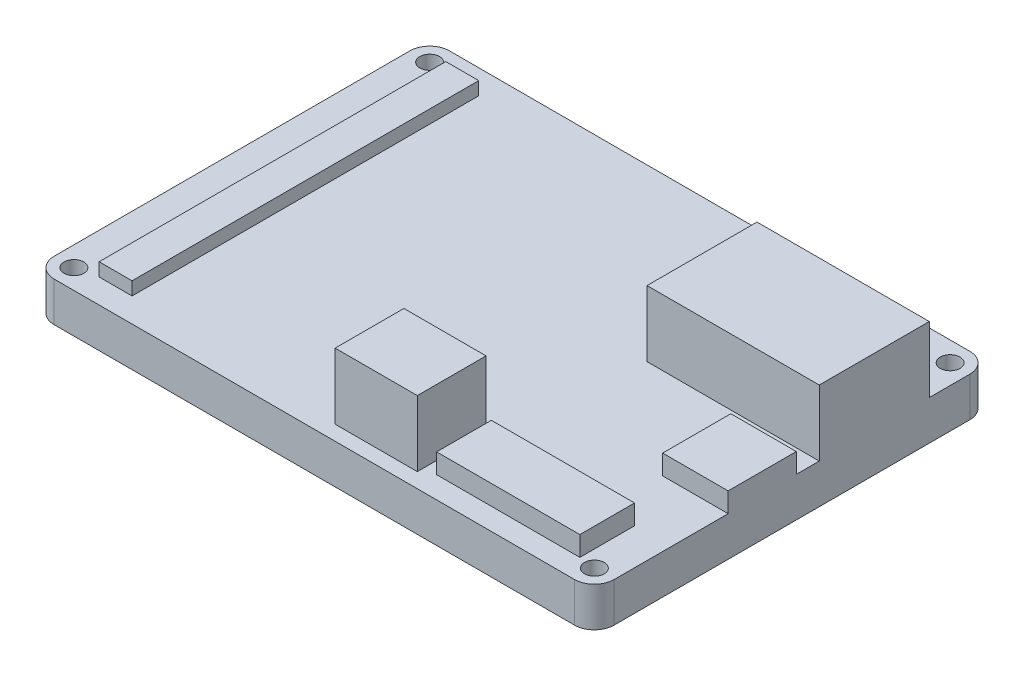
SolidWorks part; units mm, degrees
ref_plane "Front Plane" through (0, 0, 0) normal (0, 0, 1) x (1, 0, 0)
ref_plane "Top Plane" through (0, 0, 0) normal (0, 1, 0) x (1, 0, 0)
ref_plane "Right Plane" through (0, 0, 0) normal (1, 0, 0) x (0, 0, -1)
sketch "Sketch1" plane through (0, 0, 0) normal (0, 1, 0) x (1, 0, 0)
  line L1 (-39.5, -30) -> (39.5, -30)
  line L2 (-42.5, -27) -> (-42.5, 27)
  line L3 (-39.5, 30) -> (39.5, 30)
  line L4 (42.5, -27) -> (42.5, 27)
  line L5 (-42.5, -30) -> (42.5, 30) construction
  line L6 (-42.5, 30) -> (42.5, -30) construction
  line L7 (39.5, -27) -> (-39.5, -27) construction
  line L8 (39.5, -27) -> (39.5, 27) construction
  line L9 (39.5, 27) -> (-39.5, 27) construction
  line L10 (-39.5, -27) -> (-39.5, 27) construction
  line L11 (39.5, -27) -> (-39.5, 27) construction
  line L12 (39.5, 27) -> (-39.5, -27) construction
  arc A0 (-42.5, -27) -> (-39.5, -30) centre (-39.5, -27) ccw
  arc A1 (42.5, -27) -> (39.5, -30) centre (39.5, -27) cw
  arc A2 (42.5, 27) -> (39.5, 30) centre (39.5, 27) ccw
  arc A3 (-39.5, 30) -> (-42.5, 27) centre (-39.5, 27) ccw
  circle A4 centre (-39.5, 27) radius 1.5
  circle A5 centre (39.5, 27) radius 1.5
  circle A6 centre (39.5, -27) radius 1.5
  circle A7 centre (-39.5, -27) radius 1.5
  point P0 (0, 0)
  point P18 (0, 0)
  dimension "D3" = 3
  dimension "D4" = 3
  dimension "D1" = 85
  dimension "D2" = 60
extrude "Boss-Extrude1" add sketch "Sketch1" along normal blind 3 and the other way blind 3
sketch "Sketch2" plane through (0, 0, 0) normal (0, 1, 0) x (1, 0, 0)
  line L1 (-31.3605, -26.3126) -> (-36.3605, -26.3126)
  line L2 (-31.3605, -26.3126) -> (-31.3605, 26.3126)
  line L3 (-31.3605, 26.3126) -> (-36.3605, 26.3126)
  line L4 (-36.3605, -26.3126) -> (-36.3605, 26.3126)
  line L5 (-31.3605, -26.3126) -> (-36.3605, 26.3126) construction
  line L6 (-31.3605, 26.3126) -> (-36.3605, -26.3126) construction
  point P0 (-33.8605, 0)
  dimension "D1" = 5
extrude "Boss-Extrude2" add sketch "Sketch2" along normal blind 5
sketch "Sketch3" plane through (0, 0, 0) normal (0, 1, 0) x (1, 0, 0)
  line L0 (42.5, -27) -> (42.5, 27) construction
  line L1 (16.3563, 4.1414) -> (42.5, 4.1414)
  line L2 (16.3563, 4.1414) -> (16.3563, 20.8379)
  line L3 (16.3563, 20.8379) -> (42.5, 20.8379)
  line L4 (42.5, 4.1414) -> (42.5, 20.8379)
  line L5 (16.3563, 4.1414) -> (42.5, 20.8379) construction
  line L6 (16.3563, 20.8379) -> (42.5, 4.1414) construction
  point P0 (29.4281, 12.4897)
extrude "Boss-Extrude3" add sketch "Sketch3" along normal blind 13
sketch "Sketch4" plane through (0, 0, 0) normal (0, 1, 0) x (1, 0, 0)
  line L0 (42.5, -27) -> (42.5, 27) construction
  line L1 (32.5617, -9.692) -> (42.5, -9.692)
  line L2 (32.5617, -9.692) -> (32.5617, 0.6529)
  line L3 (32.5617, 0.6529) -> (42.5, 0.6529)
  line L4 (42.5, -9.692) -> (42.5, 0.6529)
  line L5 (32.5617, -9.692) -> (42.5, 0.6529) construction
  line L6 (32.5617, 0.6529) -> (42.5, -9.692) construction
  point P0 (37.5309, -4.5195)
extrude "Boss-Extrude4" add sketch "Sketch4" along normal blind 6
sketch "Sketch5" plane through (0, 0, 0) normal (0, 1, 0) x (1, 0, 0)
  line L1 (0.9075, -17.3194) -> (13.3809, -17.3194)
  line L2 (0.9075, -17.3194) -> (0.9075, -27.7522)
  line L3 (0.9075, -27.7522) -> (13.3809, -27.7522)
  line L4 (13.3809, -17.3194) -> (13.3809, -27.7522)
  line L5 (0.9075, -17.3194) -> (13.3809, -27.7522) construction
  line L6 (0.9075, -27.7522) -> (13.3809, -17.3194) construction
  point P0 (7.1442, -22.5358)
extrude "Boss-Extrude5" add sketch "Sketch5" along normal blind 13
sketch "Sketch6" plane through (0, 0, 0) normal (0, 1, 0) x (1, 0, 0)
  line L1 (15.2482, -18.3865) -> (36.9873, -18.3865)
  line L2 (15.2482, -18.3865) -> (15.2482, -26.6879)
  line L3 (15.2482, -26.6879) -> (36.9873, -26.6879)
  line L4 (36.9873, -18.3865) -> (36.9873, -26.6879)
  line L5 (15.2482, -18.3865) -> (36.9873, -26.6879) construction
  line L6 (15.2482, -26.6879) -> (36.9873, -18.3865) construction
  point P0 (26.1178, -22.5372)
extrude "Boss-Extrude6" add sketch "Sketch6" along normal blind 6
